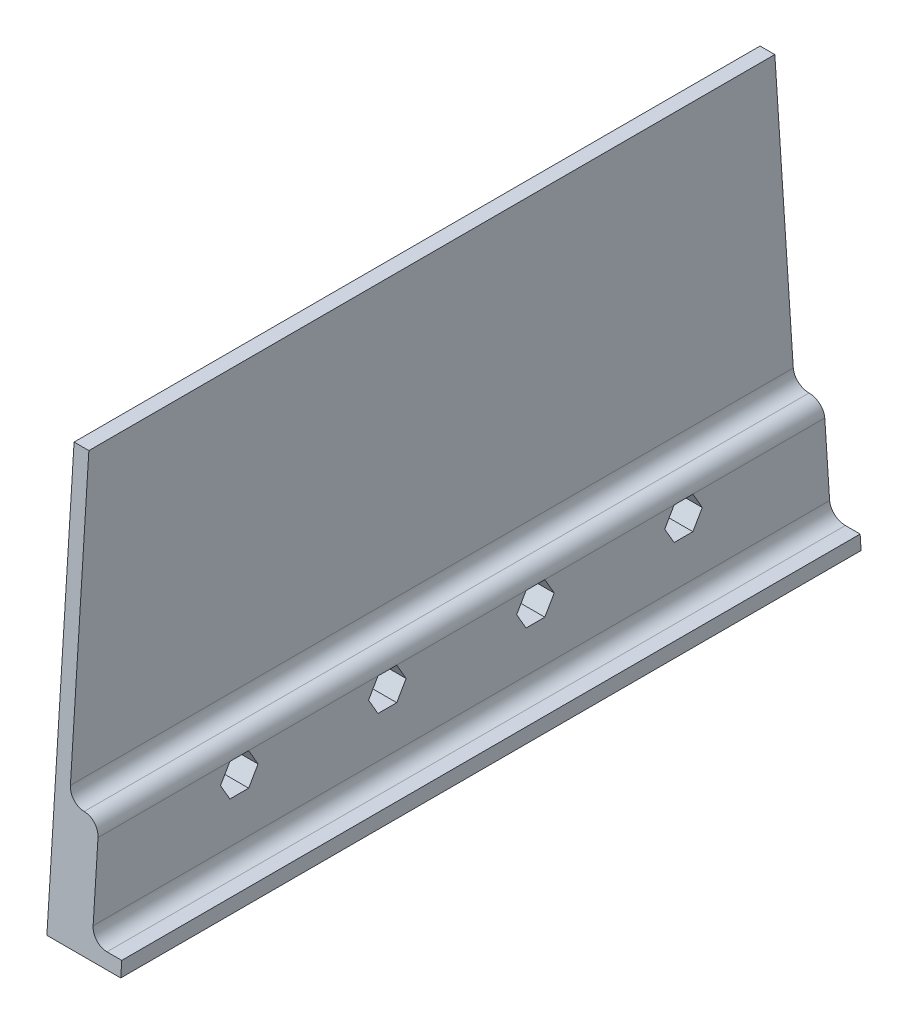
SolidWorks part; units mm, degrees
material "AISI 4340 Steel, annealed"
ref_plane "Front Plane" through (0, 0, 0) normal (0, 0, 1) x (1, 0, 0)
ref_plane "Top Plane" through (0, 0, 0) normal (0, 1, 0) x (1, 0, 0)
ref_plane "Right Plane" through (0, 0, 0) normal (1, 0, 0) x (0, 0, -1)
sketch "Sketch2" plane through (0, 0, 0) normal (0, 0, 1) x (1, 0, 0)
  line L0 (-12.5, 20) -> (12.5, -20) construction
  line L5 (-12.5, -20) -> (12.5, 20) construction
  line L6 (-12.5, 20) -> (-12.5, -20)
  line L7 (-12.5, -20) -> (12.5, -20)
  line L8 (12.5, -20) -> (12.5, -15)
  line L9 (12.5, -15) -> (2.5, -15)
  line L10 (2.5, -15) -> (2.5, 20)
  line L11 (2.5, 20) -> (-12.5, 20)
  point P4 (0, 0)
  point P6 (0, 0)
  dimension "D1" = 25
  dimension "D2" = 40
  dimension "D3" = 15
  dimension "D4" = 5
extrude "General extrude" add sketch "Sketch2" along normal mid plane 250.6
fillet "Rounding" radius 5 2 edges at (2.5, 20, 0) (2.5, -15, 0)
sketch "Sketch3" plane through (-12.5, 0, 0) normal (-1, 0, 0) x (0, 0, 1)
  line L0 (125.3, -20) -> (-125.3, -20) construction
  line L211 (-72.0046, 4) -> (-68.8291, 9.5)
  line L212 (125.3, 20) -> (125.3, -20) construction
  line L214 (-68.8291, 9.5) -> (-72.0046, 15)
  line L216 (-72.0046, 15) -> (-78.3554, 15)
  line L217 (-78.3554, 15) -> (-81.5309, 9.5)
  line L218 (-81.5309, 9.5) -> (-78.3554, 4)
  line L219 (-78.3554, 4) -> (-72.0046, 4)
  line L220 (125.3, 20) -> (-125.3, 20) construction
  line L221 (-125.3, 20) -> (-125.3, -20) construction
  line L222 (-21.8846, 4) -> (-18.7091, 9.5)
  line L223 (-18.7091, 9.5) -> (-21.8846, 15)
  line L224 (-21.8846, 15) -> (-28.2354, 15)
  line L225 (-28.2354, 15) -> (-31.4109, 9.5)
  line L226 (-31.4109, 9.5) -> (-28.2354, 4)
  line L227 (-28.2354, 4) -> (-21.8846, 4)
  line L228 (28.2354, 4) -> (31.4109, 9.5)
  line L229 (31.4109, 9.5) -> (28.2354, 15)
  line L230 (28.2354, 15) -> (21.8846, 15)
  line L231 (21.8846, 15) -> (18.7091, 9.5)
  line L232 (18.7091, 9.5) -> (21.8846, 4)
  line L233 (21.8846, 4) -> (28.2354, 4)
  line L234 (78.3554, 4) -> (81.5309, 9.5)
  line L235 (81.5309, 9.5) -> (78.3554, 15)
  line L236 (78.3554, 15) -> (72.0046, 15)
  line L237 (72.0046, 15) -> (68.8291, 9.5)
  line L238 (68.8291, 9.5) -> (72.0046, 4)
  line L239 (72.0046, 4) -> (78.3554, 4)
  circle A0 centre (-75.18, 9.5) radius 5.5 construction
  circle A1 centre (75.18, 9.5) radius 5.5 construction
  point P14 (0, 0)
  point P35 (0, 0)
  point P36 (0, 0)
  point P37 (75.18, 15)
  dimension "D1" = 11
  dimension "D2" = 5
  dimension "D4" = 4
  dimension "D5" = 50.12
  dimension "D3" = 50.12
extrude "Roller holders" cut sketch "Sketch3" against normal through all
sketch "Sketch5" plane through (0, 20, 0) normal (0, 1, 0) x (1, 0, 0)
  line L0 (-2.5, -125.3) -> (-12.5, -125.3) construction
  line L1 (-12.5, 125.3) -> (-7.5, 125.3)
  line L2 (-12.5, 125.3) -> (-12.5, -125.3)
  line L3 (-12.5, -125.3) -> (-7.5, -125.3)
  line L4 (-7.5, 125.3) -> (-7.5, -125.3)
  dimension "D1" = 5
extrude "Guard rail" add sketch "Sketch5" along normal blind 100
fillet "Guard rail support fillet" radius 5 1 edges at (-7.5, 20, 0)
sketch "Sketch6" plane through (-7.5, 0, 0) normal (1, 0, 0) x (0, 0, -1)
  line L0 (-125.3, 120) -> (-125.3, -20)
  line L1 (-125.3, -20) -> (-116.0938, 120)
  line L2 (-125.3, 120) -> (125.3, 120) construction
  line L3 (-116.0938, 120) -> (-125.3, 120)
  line L4 (-121.7934, 33.325) -> (-130.3351, -96.5695) construction
extrude "Slant for input from sorter" cut sketch "Sketch6" against normal through all both and the other way through all
mirror "Mirror of cut above (since same part is used on both sides)" about plane through (0, 0, 0) normal (0, 0, 1) of "Slant for input from sorter"
